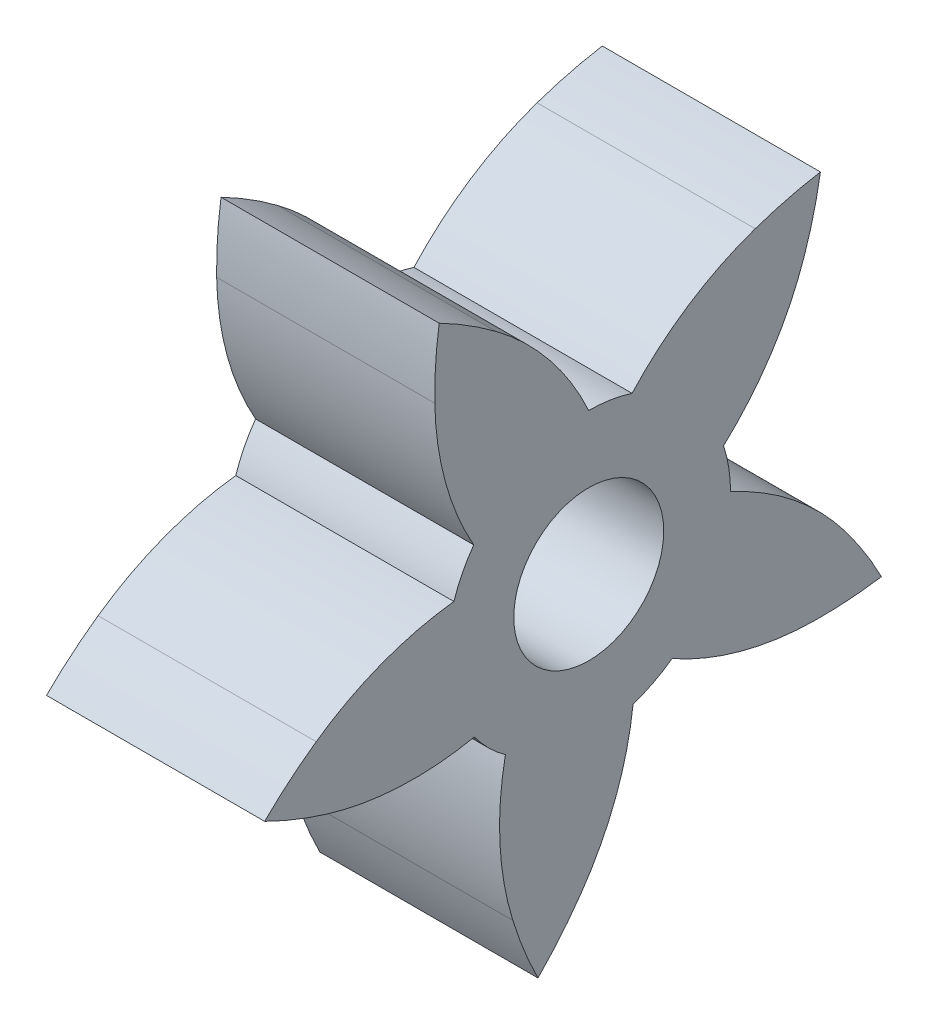
SolidWorks part; units mm, degrees
ref_plane "Front Plane" through (0, 0, 0) normal (0, 0, 1) x (1, 0, 0)
ref_plane "Top Plane" through (0, 0, 0) normal (0, 1, 0) x (1, 0, 0)
ref_plane "Right Plane" through (0, 0, 0) normal (1, 0, 0) x (0, 0, -1)
sketch "Sketch1" plane through (0, 0, 0) normal (1, 0, 0) x (0, 0, -1)
  line L0 (0, 0) -> (0, 14) construction
  line L1 (0, 0) -> (13.3148, 4.3262) construction
  line L2 (0, 0) -> (6.1046, 7.9205) construction
  line L3 (0, 0) -> (9.4193, -3.3582) construction
  line L4 (0, 0) -> (-0.2831, -9.996) construction
  line L5 (0, 0) -> (-9.5942, -2.8196) construction
  line L6 (0, 0) -> (-5.6464, 8.2534) construction
  line L7 (9.4193, -3.3582) -> (13.6372, 8.4724) construction
  line L8 (-0.2831, -9.996) -> (24.8268, -10.7073) construction
  circle A0 centre (0, 0) radius 14 construction
  circle A1 centre (0, 0) radius 10 construction
  circle A2 centre (0, 0) radius 5.2 construction
  arc A3 (9.5106, 3.0902) -> (6.1046, 7.9205) centre (0, 0) ccw construction
  arc A4 (6.1046, 7.9205) -> (24.8268, -10.7073) centre (10.909, -5.9732) cw construction
  arc A5 (6.1046, 7.9205) -> (1.5884, 4.9515) centre (9.6933, -2.4576) ccw
  arc A6 (6.1046, 7.9205) -> (10.909, 8.7277) centre (10.909, -5.9732) cw construction
  arc A7 (9.5106, 3.0902) -> (8.1726, 5.7627) centre (0, 0) ccw construction
  arc A8 (9.4193, -3.3582) -> (5.2, 0.0194) centre (0.6581, -9.9783) ccw
  arc A9 (9.4193, -3.3582) -> (10.7366, -5.4453) centre (-2.3098, -12.2209) cw
  arc A10 (5.2, 0.0194) -> (4.9455, 1.6069) centre (0, 0) ccw
  arc A11 (1.5884, 4.9515) -> (0, 5.2) centre (0, 0) ccw
  arc A12 (-0.2831, -9.996) -> (1.6254, -4.9395) centre (-9.2866, -3.7093) ccw
  arc A13 (-0.2831, -9.996) -> (-1.861, -11.8939) centre (-12.3365, -1.5797) cw
  arc A14 (1.6254, -4.9395) -> (3.0565, -4.2069) centre (0, 0) ccw
  arc A15 (-9.5942, -2.8196) -> (-4.1954, -3.0722) centre (-6.3975, 7.6858) ccw
  arc A16 (-2.7838, -9.6047) -> (-1.861, -11.8939) centre (11.2643, -5.2725) ccw
  arc A17 (-4.1954, -3.0722) -> (-3.0565, -4.2069) centre (0, 0) ccw
  arc A18 (-5.6464, 8.2534) -> (-4.2183, 3.0407) centre (5.3327, 8.4594) ccw
  arc A19 (-3.0565, -4.2069) -> (-2.7838, -9.6047) centre (7.7097, -6.3687) ccw
  arc A20 (-4.2183, 3.0407) -> (-4.9455, 1.6069) centre (0, 0) ccw
  arc A21 (3.0565, -4.2069) -> (8.2744, -5.6155) centre (8.4395, 5.3643) ccw
  arc A22 (8.2744, -5.6155) -> (10.7366, -5.4453) centre (8.4954, 9.0837) ccw
  arc A23 (-0.2831, -9.996) -> (-3.6955, -13.473) centre (-12.3365, -1.5797) cw [skipped]
  arc A24 (-9.5942, -2.8196) -> (-13.9556, -0.6487) centre (-5.3146, 11.2445) cw [skipped]
  arc A25 (-5.6464, 8.2534) -> (-4.9295, 13.0721) centre (9.0519, 8.5293) cw [skipped]
  arc A26 (-9.5942, -2.8196) -> (-11.8868, -1.9055) centre (-5.3146, 11.2445) cw
  arc A27 (-9.9949, -0.3205) -> (-11.8868, -1.9055) centre (-1.5336, -12.3423) ccw
  arc A28 (-4.9455, 1.6069) -> (-9.9949, -0.3205) centre (-3.6746, -9.3004) ccw
  arc A29 (-5.6464, 8.2534) -> (-5.4854, 10.7162) centre (9.0519, 8.5293) cw
  arc A30 (-3.3934, 9.4066) -> (-5.4854, 10.7162) centre (-12.2122, -2.3554) ccw
  arc A31 (0, 5.2) -> (-3.3934, 9.4066) centre (-9.9807, 0.6208) ccw
  arc A32 (6.1046, 7.9205) -> (8.4966, 8.5284) centre (10.909, -5.9732) cw
  arc A33 (7.8976, 6.1341) -> (8.4966, 8.5284) centre (-6.0139, 10.8866) ccw
  arc A34 (4.9455, 1.6069) -> (7.8976, 6.1341) centre (-2.4938, 9.6841) ccw
  circle A35 centre (0, 0) radius 2.75
  dimension "D1" = 28
  dimension "D2" = 20
  dimension "D3" = 10.4
  dimension "D5" = 6
  dimension "D9" = 5
  dimension "D11" = 5.5
  dimension "D4" = 72
  dimension "D7" = 12.56
  dimension "D8" = 25.12
  dimension "D6" = 5
  dimension "D10" = 5
extrude "Boss-Extrude1" add sketch "Sketch1" along normal blind 4 and the other way blind 4
